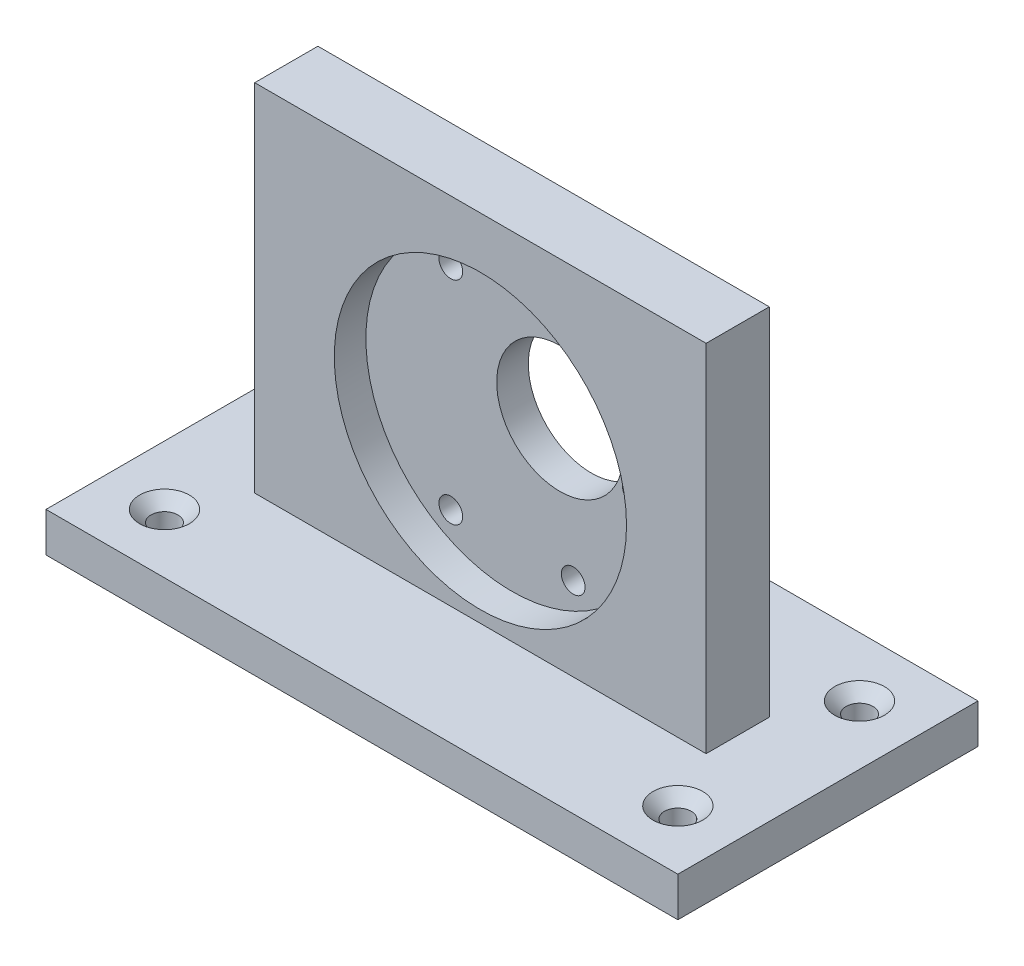
SolidWorks part; units mm, degrees
other "Markup1"
sketch "Sketch5" plane through (25, 50, 8) normal (0.9645, 0.1424, 0.2224) x (0.1697, 0.3107, -0.9352)
ref_plane "Front Plane" through (0, 0, 0) normal (0, 0, 1) x (1, 0, 0)
ref_plane "Top Plane" through (0, 0, 0) normal (0, 1, 0) x (1, 0, 0)
ref_plane "Right Plane" through (0, 0, 0) normal (1, 0, 0) x (0, 0, -1)
sketch "Sketch3" plane through (0, 0, 0) normal (0, 0, 1) x (1, 0, 0)
  line L1 (-28.575, 50) -> (28.575, 50)
  line L2 (-28.575, 50) -> (-28.575, 0)
  line L3 (-28.575, 0) -> (28.575, 0)
  line L4 (28.575, 50) -> (28.575, 0)
  line L5 (-7.75, 38.4234) -> (7.75, 38.4234) construction
  line L6 (7.75, 38.4234) -> (15.5, 25) construction
  line L7 (15.5, 25) -> (7.75, 11.5766) construction
  line L8 (7.75, 11.5766) -> (-7.75, 11.5766) construction
  line L9 (-7.75, 11.5766) -> (-15.5, 25) construction
  line L10 (-15.5, 25) -> (-7.75, 38.4234) construction
  line L12 (-20.1843, 13.3466) -> (22.8058, 38.167) construction
  circle A5 centre (-7.75, 38.4234) radius 1.5
  circle A6 centre (7.75, 38.4234) radius 1.5
  circle A8 centre (-7.75, 11.5766) radius 1.5
  circle A9 centre (7.75, 11.5766) radius 1.5
  circle A10 centre (15.5, 25) radius 1.5
  circle A11 centre (6.0622, 28.5) radius 8
  point P4 (0, 0)
  point P27 (-11.625, 18.2883)
  point P28 (11.625, 31.7117)
  dimension "D4" = 25
  dimension "D9" = 16
  dimension "D3" = 3
  dimension "D1" = 50
  dimension "D2" = 57.15
  dimension "D6" = 120
  dimension "D7" = 120
  dimension "D8" = 15.5
  dimension "D10" = 6.4234
extrude "Boss-Extrude1" add sketch "Sketch3" along normal blind 8 contours L2 L3 L4 L1
extrude "Cut-Extrude2" cut sketch "Sketch3<3>" along normal blind 10 contours A6 | A5 | A8 | A9 | A10 | A11
sketch "Sketch3<3>" plane through (0, 0, 0) normal (0, 0, 1) x (1, 0, 0) same geometry as "Sketch3"
sketch "Sketch4" plane through (0, 0, 8) normal (0, 0, 1) x (1, 0, 0)
  line L0 (-15.5, 25) -> (15.5, 25) construction
  circle A0 centre (0, 25) radius 18.5
  dimension "D1" = 37
extrude "Cut-Extrude3" cut sketch "Sketch4" against normal blind 4 contours A0
sketch "Sketch6" plane through (0, 0, 8) normal (0, 0, 1) x (1, 0, 0)
  line L1 (-40, 5) -> (40, 5)
  line L2 (-40, 5) -> (-40, 0)
  line L3 (-40, 0) -> (40, 0)
  line L4 (40, 5) -> (40, 0)
  point P4 (0, 0)
  dimension "D1" = 80
  dimension "D2" = 5
extrude "Boss-Extrude2" add sketch "Sketch6" against normal blind 23 and the other way blind 15
sketch "Sketch7" plane through (0, 5, 0) normal (0, 1, 0) x (1, 0, 0)
  line L0 (-40, -23) -> (-40, 15) construction
  line L1 (-40, -23) -> (-32.5, -23)
  line L2 (-40, -23) -> (-40, -15.5)
  line L3 (-40, -15.5) -> (-32.5, -15.5)
  line L4 (-32.5, -23) -> (-32.5, -15.5)
  line L5 (-40, -4) -> (40, -4) construction
  line L6 (40, -23) -> (40, 15) construction
  line L7 (0, 15) -> (0, -23) construction
  line L8 (40, 15) -> (-40, 15) construction
  line L9 (40, -23) -> (-40, -23) construction
  point P18 (-32.5, 7.5)
  point P20 (32.5, -15.5)
  point P21 (32.5, 7.5)
  dimension "D1" = 7.5
hole_wizard "CSK for M3 Flat Head Machine Screw1" positions "Sketch8" profile "Sketch9" countersink size "M3" standard "ANSI Metric" end condition through all
sketch "Sketch8" plane through (0, 5, 0) normal (0, 1, 0) x (1, 0, 0)
  point P0 (-32.5, 7.5)
  point P3 (-32.5, -15.5)
  point P6 (32.5, -15.5)
  point P9 (32.5, 7.5)
sketch "Sketch9" plane through (-32.5, 5, -7.5) normal (1, 0, 0) x (0, 0, 1)
  line L0 (0, 0) -> (0, 5)
  line L1 (0, 5) -> (1.7, 5)
  line L2 (1.7, 5) -> (1.7, 1.45)
  line L3 (1.7, 1.45) -> (3.15, 0)
  line L5 (3.15, 0) -> (0, 0)
  line L6 (-1.7, 1.45) -> (-3.15, 0) construction
  line L11 (0, -6.35) -> (0, 107.95) construction
  dimension "Thru Hole Dia." = 3.4
  dimension "Thru Hole Depth" = 5
  dimension "Near C'Sink Dia." = 6.3
  dimension "Near C'Sink Angle" = 90
sketch "Sketch13" plane through (0, 0, 0) normal (0, 0, -1) x (-1, 0, 0)
  line L0 (20.564, 28.5) -> (12.944, 28.5) construction
  line L1 (20.564, 23.293) -> (12.944, 23.293)
  line L2 (20.564, 33.707) -> (12.944, 33.707)
  line L3 (-28.575, 5) -> (28.575, 5) construction
  line L4 (20.564, 22.023) -> (12.944, 22.023)
  line L5 (20.564, 34.977) -> (12.944, 34.977)
  arc A0 (20.564, 23.293) -> (20.564, 33.707) centre (20.564, 28.5) ccw
  arc A1 (12.944, 33.707) -> (12.944, 23.293) centre (12.944, 28.5) ccw
  arc A2 (12.944, 34.977) -> (12.944, 22.023) centre (12.944, 28.5) ccw
  arc A3 (20.564, 22.023) -> (20.564, 34.977) centre (20.564, 28.5) ccw
  point P2 (16.754, 28.5)
  dimension "D1" = 5.207
  dimension "D2" = 20.564
  dimension "D3" = 23.5
  dimension "D4" = 7.62
  dimension "D5" = 1.27
extrude "Boss-Extrude4" add sketch "Sketch13" along normal blind 2.54
